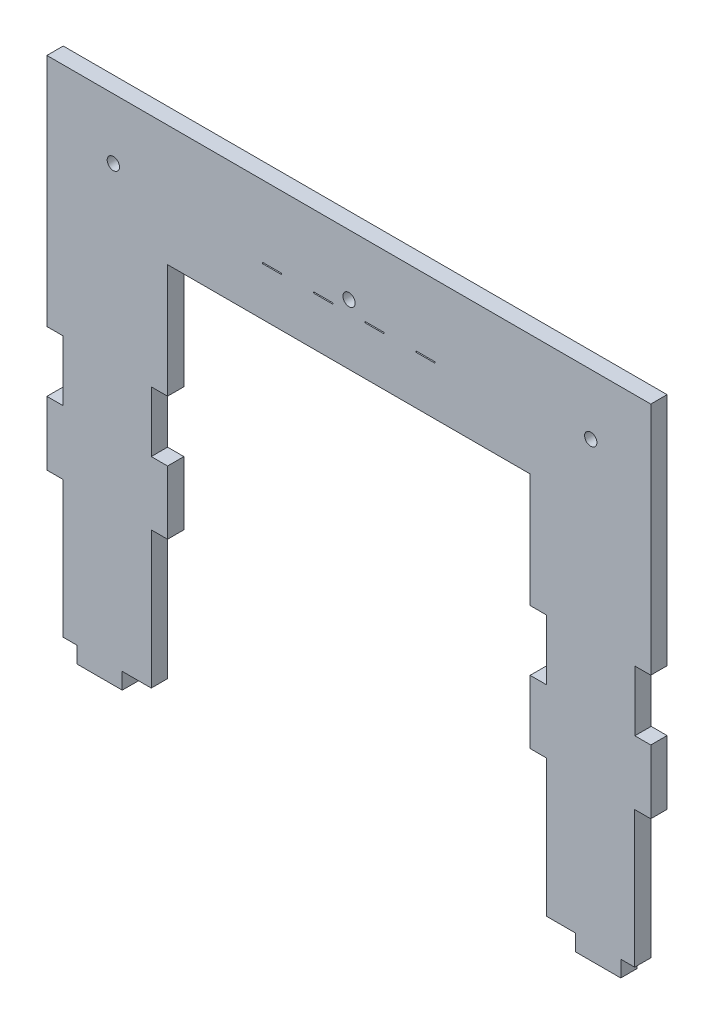
SolidWorks part; units mm, degrees
ref_plane "Front Plane" through (0, 0, 0) normal (0, 0, 1) x (1, 0, 0)
ref_plane "Top Plane" through (0, 0, 0) normal (0, 1, 0) x (1, 0, 0)
ref_plane "Right Plane" through (0, 0, 0) normal (1, 0, 0) x (0, 0, -1)
sketch "Sketch1" plane through (0, 0, 0) normal (0, 0, 1) x (1, 0, 0)
  line L0 (-34.5174, -9.4807) -> (-34.5174, 13.2011)
  line L1 (-34.5174, 13.2011) -> (-31.8174, 13.2011)
  line L2 (-31.8174, 13.2011) -> (-31.8174, 23.7011)
  line L3 (-31.8174, 23.7011) -> (-34.5174, 23.7011)
  line L4 (-34.5174, 23.7011) -> (-34.5174, 33.7011)
  line L5 (-34.5174, 33.7011) -> (-31.8174, 33.7011)
  line L6 (-31.8174, 33.7011) -> (-31.8174, 52.5613)
  line L7 (-51.785, 72.5613) -> (48.1502, 72.5613)
  line L8 (-1.8174, 52.5613) -> (-1.8174, 3.2011) construction
  line L9 (-34.5174, -9.4807) -> (-39.3174, -9.4807)
  line L10 (-39.3174, -9.4807) -> (-39.3174, -12.1807)
  line L11 (-39.3174, -12.1807) -> (-46.8174, -12.1807)
  line L12 (-46.8174, -12.1807) -> (-46.8174, -9.4807)
  line L13 (-46.8174, -9.4807) -> (-49.1174, -9.4807)
  line L14 (-51.785, 13.1219) -> (-51.785, 23.7011)
  line L15 (-31.8174, 52.5613) -> (28.1826, 52.5613)
  line L16 (9.3001, 60.5613) -> (-12.9349, 60.5613) construction
  line L17 (-12.9349, 60.7613) -> (-16.1099, 60.7613)
  line L18 (-12.9349, 60.7613) -> (-12.9349, 60.5613)
  line L19 (-12.9349, 60.5613) -> (-16.1099, 60.5613)
  line L20 (-16.1099, 60.7613) -> (-16.1099, 60.5613)
  line L21 (-4.4649, 60.7613) -> (-7.6399, 60.7613)
  line L22 (-4.4649, 60.7613) -> (-4.4649, 60.5613)
  line L23 (-4.4649, 60.5613) -> (-7.6399, 60.5613)
  line L24 (-49.1174, 13.1219) -> (-49.1174, -9.4807)
  line L25 (43.1826, -9.4807) -> (45.4826, -9.4807)
  line L26 (43.1826, -12.1807) -> (43.1826, -9.4807)
  line L27 (35.6826, -12.1807) -> (43.1826, -12.1807)
  line L28 (35.6826, -9.4807) -> (35.6826, -12.1807)
  line L29 (30.8826, -9.4807) -> (35.6826, -9.4807)
  line L30 (28.1826, 33.7011) -> (28.1826, 52.5613)
  line L31 (30.8826, 33.7011) -> (28.1826, 33.7011)
  line L32 (30.8826, 23.7011) -> (30.8826, 33.7011)
  line L33 (28.1826, 23.7011) -> (30.8826, 23.7011)
  line L34 (28.1826, 13.2011) -> (28.1826, 23.7011)
  line L35 (30.8826, 13.2011) -> (28.1826, 13.2011)
  line L36 (30.8826, -9.4807) -> (30.8826, 13.2011)
  line L37 (-7.6399, 60.7613) -> (-7.6399, 60.5613)
  line L38 (4.0051, 60.7613) -> (0.8301, 60.7613)
  line L39 (4.0051, 60.7613) -> (4.0051, 60.5613)
  line L40 (4.0051, 60.5613) -> (0.8301, 60.5613)
  line L41 (0.8301, 60.7613) -> (0.8301, 60.5613)
  line L42 (12.4751, 60.7613) -> (9.3001, 60.7613)
  line L43 (12.4751, 60.7613) -> (12.4751, 60.5613)
  line L44 (12.4751, 60.5613) -> (9.3001, 60.5613)
  line L45 (9.3001, 60.7613) -> (9.3001, 60.5613)
  line L46 (-46.785, -12.1807) -> (-39.285, -12.1807) construction
  line L47 (45.515, 23.7011) -> (48.1502, 23.7011)
  line L48 (-51.785, 52.5613) -> (-51.785, 72.5613) construction
  line L49 (48.1502, 33.7011) -> (48.1502, 72.5613)
  line L51 (45.515, 23.7011) -> (45.515, 33.7011)
  line L52 (45.515, 33.7011) -> (48.1502, 33.7011)
  line L53 (45.4826, 13.1219) -> (48.1502, 13.1219)
  line L54 (48.1502, 23.7011) -> (48.1502, 13.1219)
  line L55 (-49.1174, 13.1219) -> (-51.785, 13.1219)
  line L57 (-49.1498, 23.7011) -> (-51.785, 23.7011)
  line L58 (-49.1498, 23.7011) -> (-49.1498, 33.7011)
  line L59 (45.4826, 13.1219) -> (45.4826, -9.4807)
  line L60 (-49.1498, 33.7011) -> (-51.785, 33.7011)
  line L61 (-51.785, 33.7011) -> (-51.785, 72.5613)
  circle A1 centre (-40.7925, 62.5613) radius 1.016
  circle A2 centre (38.215, 62.5613) radius 1.016
  circle A3 centre (-1.785, 62.5613) radius 1.016
  point P20 (-1.8174, 72.5613)
  point P26 (-1.8174, 72.5613)
  point P27 (-1.8174, 60.5613)
  dimension "D4" = 4
  dimension "D1" = 2.7
  dimension "D2" = 30
  dimension "D3" = 30.5
  dimension "D5" = 3.175
  dimension "D6" = 0.2
  dimension "D7" = 20
  dimension "D8" = 8
  dimension "D9" = 2.7
  dimension "D11" = 7.5
  dimension "D17" = 4.8
extrude "Base" add sketch "Sketch1" along normal blind 2.7
